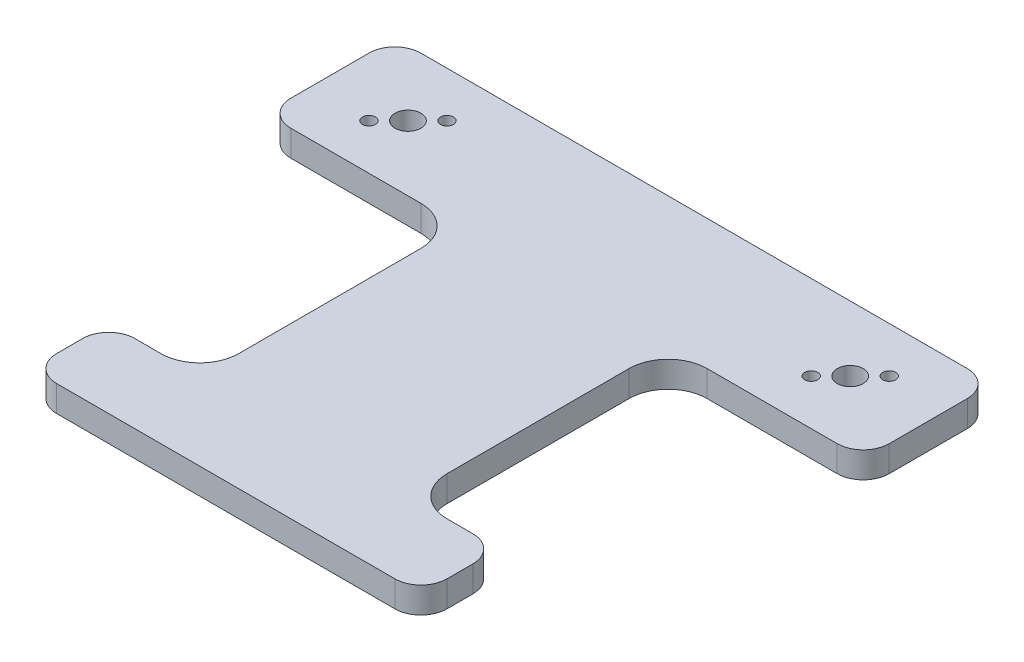
SolidWorks part; units mm, degrees
ref_plane "Vorne" through (0, 0, 0) normal (0, 0, 1) x (1, 0, 0)
ref_plane "Oben" through (0, 0, 0) normal (0, 1, 0) x (1, 0, 0)
ref_plane "Rechts" through (0, 0, 0) normal (1, 0, 0) x (0, 0, -1)
ref_plane "E_Boden" through (0, 1, 0) normal (0, 1, 0) x (1, 0, 0)
sketch "Skizze1" plane through (0, 0, 0) normal (0, 1, 0) x (1, 0, 0)
  line L0 (0, -84.2382) -> (0, 127.1868) construction
  line L1 (-165.4867, 0) -> (188.3198, 0) construction
  line L2 (-105, 90) -> (105, 90)
  line L3 (-115, 80) -> (-115, 50)
  line L8 (-105, 40) -> (-55, 40)
  line L9 (-40, 25) -> (-40, -45)
  line L10 (-55, -60) -> (-65, -60)
  line L11 (-75, -70) -> (-75, -80)
  line L12 (-65, -90) -> (65, -90)
  line L13 (75, -70) -> (75, -80)
  line L14 (55, -60) -> (65, -60)
  line L15 (40, 25) -> (40, -45)
  line L16 (105, 40) -> (55, 40)
  line L17 (115, 80) -> (115, 50)
  arc A0 (40, 25) -> (55, 40) centre (55, 25) cw
  arc A1 (55, -60) -> (40, -45) centre (55, -45) cw
  arc A2 (-40, -45) -> (-55, -60) centre (-55, -45) cw
  arc A3 (-55, 40) -> (-40, 25) centre (-55, 25) cw
  arc A4 (75, -70) -> (65, -60) centre (65, -70) ccw
  arc A5 (75, -80) -> (65, -90) centre (65, -80) cw
  arc A6 (-75, -80) -> (-65, -90) centre (-65, -80) ccw
  arc A7 (-65, -60) -> (-75, -70) centre (-65, -70) ccw
  arc A8 (-115, 50) -> (-105, 40) centre (-105, 50) ccw
  arc A9 (105, 40) -> (115, 50) centre (105, 50) ccw
  arc A10 (115, 80) -> (105, 90) centre (105, 80) ccw
  arc A11 (-105, 90) -> (-115, 80) centre (-105, 80) ccw
  point P15 (0, -90)
  point P16 (0, 90)
  point P22 (40, 40)
  point P25 (40, -60)
  point P28 (-40, -60)
  point P31 (-40, 40)
  point P34 (75, -60)
  point P37 (75, -90)
  point P40 (-75, -90)
  point P43 (-75, -60)
  point P46 (-115, 40)
  point P49 (115, 40)
  point P52 (115, 90)
  point P55 (-115, 90)
  dimension "D7" = 15
  dimension "D8" = 10
  dimension "D1" = 230
  dimension "D2" = 50
  dimension "D3" = 130
  dimension "D4" = 150
  dimension "D5" = 80
  dimension "D6" = 30
extrude "Aufsatz-Linear austragen1" add sketch "Skizze1" along normal blind 10
hole_wizard "Ø10.0 (10) Durchmesser Bohrung1" positions "Skizze6" profile "Skizze7" hole size "Ø10.0" standard "DIN" end condition through all
sketch "Skizze6" plane through (0, 10, 0) normal (0, 1, 0) x (1, 0, 0)
  line L2 (105, 90) -> (-105, 90) construction
  line L3 (0, 90) -> (0, -90) construction
  line L4 (-65, -90) -> (65, -90) construction
  point P0 (-85, 65)
  point P2 (85, 65)
  dimension "D1" = 25
  dimension "D2" = 25
  dimension "D3" = 170
sketch "Skizze7" plane through (-85, 10, -65) normal (1, 0, 0) x (0, 0, 1)
  line L0 (0, 0) -> (0, 10)
  line L1 (0, 10) -> (5, 10)
  line L2 (5, 10) -> (5, 0)
  line L5 (5, 0) -> (0, 0)
  line L11 (0, -6.35) -> (0, 107.95) construction
  dimension "Bohrerdurchmesser" = 10
  dimension "Bohrungstiefe" = 10
hole_wizard "Ø5.0 (5) Durchmesser Bohrung1" positions "Skizze11" profile "Skizze12" hole size "Ø5.0" standard "DIN" end condition through all
sketch "Skizze11" plane through (0, 0, 0) normal (0, -1, 0) x (-1, 0, 0)
  line L0 (77.5, 72.5) -> (77.5, 45.1453) construction
  line L3 (92.5, 57.5) -> (92.5, 79.091) construction
  line L6 (-92.5, 72.5) -> (-92.5, 57.5) construction
  line L9 (-77.5, 57.5) -> (-77.5, 72.5) construction
  line L12 (-77.5, 57.5) -> (-92.5, 57.5) construction
  line L15 (-77.5, 72.5) -> (-92.5, 72.5) construction
  line L18 (77.5, 72.5) -> (92.5, 72.5) construction
  line L21 (92.5, 57.5) -> (77.5, 57.5) construction
  line L24 (80, 65) -> (71.5087, 65) construction
  line L25 (71.5087, 65) -> (96.6058, 65) construction
  line L28 (85, 60) -> (85, 53.6887) construction
  line L29 (85, 53.6887) -> (85, 75.0654) construction
  line L30 (-90, 65) -> (-74.1442, 65) construction
  line L32 (-85, 70) -> (-85, 55.7381) construction
  circle A0 centre (85, 65) radius 5 construction
  circle A1 centre (-85, 65) radius 5 construction
  point P0 (77.5, 72.5)
  point P2 (92.5, 57.5)
  point P4 (-92.5, 72.5)
  point P6 (-77.5, 57.5)
  point P43 (85, 72.5)
  point P67 (-92.7982, 57.5)
  point P68 (0, 0)
  point P69 (-77.4099, 72.5)
  point P70 (-79.4801, 72.5339)
  point P71 (-92.1082, 72.3959)
  point P72 (-78.238, 57.8356)
  dimension "D1" = 15
  dimension "D2" = 15
  dimension "D3" = 7.5
  dimension "D4" = 7.5
  dimension "D5" = 15
  dimension "D6" = 15
  dimension "D7" = 7.5
  dimension "D8" = 7.5
sketch "Skizze12" plane through (-77.5, 0, -72.5) normal (1, 0, 0) x (0, 0, -1)
  line L0 (0, 0) -> (0, 10)
  line L1 (0, 10) -> (2.5, 10)
  line L2 (2.5, 10) -> (2.5, 0)
  line L5 (2.5, 0) -> (0, 0)
  line L11 (0, -6.35) -> (0, 107.95) construction
  dimension "Bohrerdurchmesser" = 5
  dimension "Bohrungstiefe" = 10
